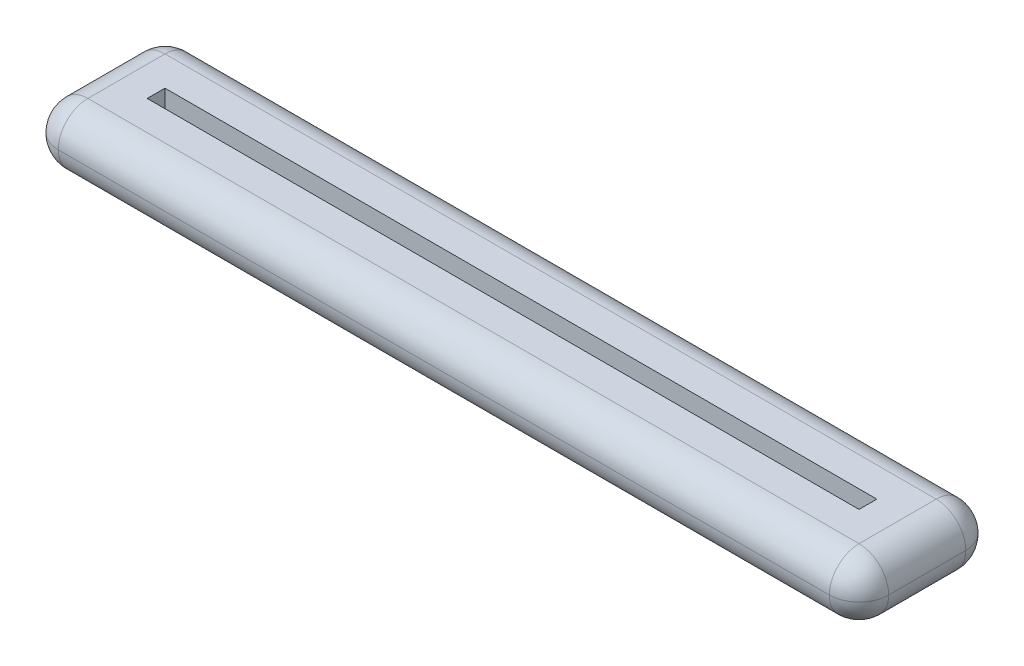
SolidWorks part; units mm, degrees
ref_plane "Plan de face" through (0, 0, 0) normal (0, 0, 1) x (1, 0, 0)
ref_plane "Plan de dessus" through (0, 0, 0) normal (0, 1, 0) x (1, 0, 0)
ref_plane "Plan de droite" through (0, 0, 0) normal (1, 0, 0) x (0, 0, -1)
sketch "Esquisse4" plane through (0, 0, 0) normal (0, 1, 0) x (1, 0, 0)
  line L1 (-35, -5.75) -> (35, -5.75)
  line L2 (-35, -5.75) -> (-35, 5.75)
  line L3 (-35, 5.75) -> (35, 5.75)
  line L4 (35, -5.75) -> (35, 5.75)
  line L5 (-35, -5.75) -> (35, 5.75) construction
  line L6 (-35, 5.75) -> (35, -5.75) construction
  line L7 (-30, -0.75) -> (30, -0.75)
  line L8 (-30, -0.75) -> (-30, 0.75)
  line L9 (-30, 0.75) -> (30, 0.75)
  line L10 (30, -0.75) -> (30, 0.75)
  line L11 (-30, -0.75) -> (30, 0.75) construction
  line L12 (-30, 0.75) -> (30, -0.75) construction
  point P0 (0, 0)
  point P6 (0, 0)
  dimension "D1" = 11.5
  dimension "D2" = 70
  dimension "D3" = 1.5
  dimension "D4" = 60
extrude "Boss.-Extru.2" add sketch "Esquisse4" along normal blind 5
fillet "Congé1" radius 2.5 12 edges at (-35, 2.5, 5.75) (-35, 2.5, -5.75) (35, 2.5, 5.75) (-35, 5, 0) (0, 5, 5.75) (35, 5, 0) (0, 5, -5.75) (35, 2.5, -5.75) (35, 0, 0) (0, 0, -5.75) (-35, 0, 0) (0, 0, 5.75)
